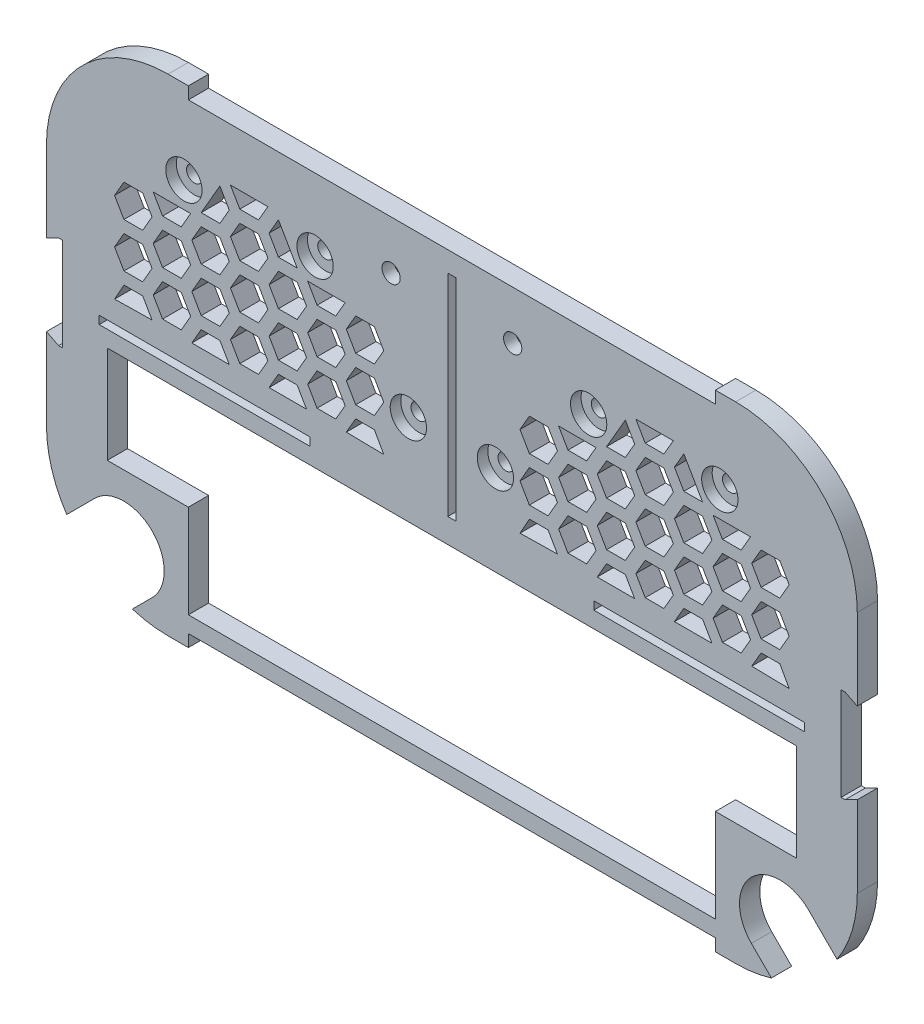
SolidWorks part; units mm, degrees
ref_plane "前视基准面" through (0, 0, 0) normal (0, 0, 1) x (1, 0, 0)
ref_plane "上视基准面" through (0, 0, 0) normal (0, 1, 0) x (1, 0, 0)
ref_plane "右视基准面" through (0, 0, 0) normal (1, 0, 0) x (0, 0, -1)
sketch "草图1" plane through (0, 0, 0) normal (0, 0, 1) x (1, 0, 0)
  line L1 (70, 60) -> (-70, 60)
  line L2 (-100, 30) -> (-100, -30)
  line L4 (70, -60) -> (-70, -60)
  line L5 (100, 30) -> (100, -30)
  arc A0 (-70, 60) -> (-100, 30) centre (-70, 30) ccw
  arc A1 (-70, -60) -> (-100, -30) centre (-70, -30) cw
  arc A2 (70, -60) -> (100, -30) centre (70, -30) ccw
  arc A3 (70, 60) -> (100, 30) centre (70, 30) cw
  point P12 (0, -60)
extrude "凸台-拉伸1" add sketch "草图1" along normal blind 5
sketch "草图2" plane through (0, 0, 0) normal (0, 0, 1) x (1, 0, 0)
  line L0 (95.0012, -46.5813) -> (95.0012, -58.6765)
  line L1 (88.021, -39.6011) -> (95.0012, -46.5813)
  line L2 (95.0012, -58.6765) -> (78.8123, -58.6765)
  line L3 (73.8789, -53.7432) -> (78.8123, -58.6765)
  line L5 (-73.8789, -53.7432) -> (-78.8123, -58.6765)
  line L6 (-95.0012, -58.6765) -> (-78.8123, -58.6765)
  line L7 (-88.021, -39.6011) -> (-95.0012, -46.5813)
  line L8 (-95.0012, -46.5813) -> (-95.0012, -58.6765)
  circle A0 centre (-80.95, 46.6721) radius 10
  circle A1 centre (80.95, 46.6721) radius 10
  arc A4 (70, -60) -> (100, -30) centre (70, -30) ccw construction
  arc A5 (-88.021, -39.6011) -> (-73.8789, -53.7432) centre (-80.95, -46.6721) cw
  arc A6 (88.021, -39.6011) -> (73.8789, -53.7432) centre (80.95, -46.6721) ccw
extrude "孔" cut sketch "草图2" along normal blind 4 contours A1 | A0 region at (-80.95, 46.6721, 0) region at (80.95, 46.6721, 0)
sketch "草图3" plane through (0, 0, 0) normal (0, 0, 1) x (1, 0, 0)
  line L8 (-85, -6) -> (-85, -30)
  line L12 (-70, -30) -> (-65, -30)
  line L22 (-85, -30) -> (-70, -30)
  line L26 (85, -30) -> (70, -30)
  line L32 (70, -30) -> (65, -30)
  line L37 (-65, -30) -> (-65, -53)
  line L39 (65, -53) -> (65, -30)
  line L40 (-65, -60) -> (-65, -57)
  line L41 (-70, -60) -> (70, -60) construction
  line L42 (-65, -57) -> (65, -57)
  line L43 (65, -57) -> (65, -60)
  line L44 (-65, -60) -> (65, -60)
  line L50 (-100, -10) -> (-97, -11.5)
  line L53 (-100, 10) -> (-100, -10)
  line L55 (-85, -6) -> (85, -6)
  line L56 (85, -6) -> (85, -30)
  line L88 (65, -53) -> (-65, -53)
  line L89 (87, 0) -> (87, -2)
  line L90 (87, -2) -> (35, -2)
  line L92 (87, 0) -> (37, 0)
  line L96 (35, 0) -> (35, -2)
  line L105 (-35, 0) -> (-35, -2)
  line L109 (-87, 0) -> (-37, 0)
  line L110 (-87, -2) -> (-35, -2)
  line L111 (-87, 0) -> (-87, -2)
  line L112 (97, 11.5) -> (96, 11.5)
  line L114 (-97, 11.5) -> (-100, 10)
  line L115 (97, 11.5) -> (100, 10)
  line L118 (100, 10) -> (100, -10)
  line L119 (100, -10) -> (97, -11.5)
  line L120 (96, 11.5) -> (96, -11.5)
  line L121 (96, -11.5) -> (97, -11.5)
  line L122 (-97, 11.5) -> (-96, 11.5)
  line L123 (-96, 11.5) -> (-96, -11.5)
  line L124 (-96, -11.5) -> (-97, -11.5)
  line L125 (0, 0) -> (-1, 0)
  line L126 (-1, 0) -> (-1, 50)
  line L128 (1, 50) -> (1, 0)
  line L129 (1, 0) -> (0, 0)
  line L130 (-1, 50) -> (-1, 52)
  line L131 (-1, 52) -> (1, 52)
  line L132 (1, 52) -> (1, 50)
  line L133 (-37, 0) -> (-35, 0)
  line L134 (35, 0) -> (37, 0)
  line L135 (-65, 57) -> (-65, 60)
  line L136 (-65, 57) -> (65, 57)
  line L138 (65, 57) -> (65, 60)
  line L139 (65, 60) -> (-65, 60)
extrude "切除-拉伸4" cut sketch "草图3" along normal up to next
hole_wizard "M3.5 六角头机械螺钉的柱形沉头孔1" positions "3D草图1" profile "草图4" counterbore size "M3.5" standard "ANSI Metric" end condition through all
sketch3d "3D草图1"
  point P31 (-66.0951, 39.3344, 5)
  point P33 (-33.736, 39.2649, 5)
  point P35 (-10.7334, 16.264, 5)
  point P78 (33.736, 39.2649, 5)
  point P80 (10.7334, 16.264, 5)
  point P82 (66.0951, 39.3344, 5)
sketch "草图4" plane through (-66.0951, 39.3344, 5) normal (1, 0, 0) x (0, -1, 0)
  line L0 (0, 0) -> (0, 5)
  line L1 (0, 5) -> (1.95, 5)
  line L3 (1.95, 5) -> (1.95, 2.6)
  line L4 (1.95, 2.6) -> (4.48, 2.6)
  line L5 (4.48, 2.6) -> (4.48, 0)
  line L7 (4.48, 0) -> (0, 0)
  line L11 (0, -6.35) -> (0, 107.95) construction
  dimension "通孔孔直径" = 3.9
  dimension "通孔孔深度" = 5
  dimension "柱形沉头孔直径" = 8.96
  dimension "柱形沉头孔深度" = 2.6
sketch "草图5" plane through (0, 0, 0) normal (0, 0, 1) x (1, 0, 0)
  line L4 (-35.8549, 5.5) -> (-38.1643, 9.5)
  line L6 (-38.1643, 9.5) -> (-42.7831, 9.5)
  line L13 (-42.7831, 9.5) -> (-45.0925, 5.5)
  line L17 (-26.3286, 11) -> (-28.638, 15)
  line L18 (-28.638, 15) -> (-33.2568, 15)
  line L19 (-33.2568, 15) -> (-35.5662, 11)
  line L20 (-35.5662, 11) -> (-33.2568, 7)
  line L21 (-33.2568, 7) -> (-28.638, 7)
  line L22 (-28.638, 7) -> (-26.3286, 11)
  line L23 (-16.8024, 16.5) -> (-19.1118, 20.5)
  line L24 (-19.1118, 20.5) -> (-23.7306, 20.5)
  line L25 (-23.7306, 20.5) -> (-26.04, 16.5)
  line L26 (-26.04, 16.5) -> (-23.7306, 12.5)
  line L27 (-23.7306, 12.5) -> (-19.1118, 12.5)
  line L28 (-19.1118, 12.5) -> (-16.8024, 16.5)
  line L29 (-35.8549, 16.5) -> (-38.1643, 20.5)
  line L30 (-38.1643, 20.5) -> (-42.7831, 20.5)
  line L31 (-42.7831, 20.5) -> (-45.0925, 16.5)
  line L32 (-45.0925, 16.5) -> (-42.7831, 12.5)
  line L33 (-42.7831, 12.5) -> (-38.1643, 12.5)
  line L34 (-38.1643, 12.5) -> (-35.8549, 16.5)
  line L35 (-26.3286, 22) -> (-28.638, 26)
  line L36 (-28.638, 26) -> (-33.2568, 26)
  line L37 (-33.2568, 26) -> (-35.5662, 22)
  line L38 (-35.5662, 22) -> (-33.2568, 18)
  line L39 (-33.2568, 18) -> (-28.638, 18)
  line L40 (-28.638, 18) -> (-26.3286, 22)
  line L41 (-16.8024, 27.5) -> (-19.1118, 31.5)
  line L42 (-19.1118, 31.5) -> (-23.7306, 31.5)
  line L43 (-23.7306, 31.5) -> (-26.04, 27.5)
  line L44 (-26.04, 27.5) -> (-23.7306, 23.5)
  line L45 (-23.7306, 23.5) -> (-19.1118, 23.5)
  line L46 (-19.1118, 23.5) -> (-16.8024, 27.5)
  line L47 (-35.8549, 27.5) -> (-38.1643, 31.5)
  line L48 (-38.1643, 31.5) -> (-42.7831, 31.5)
  line L49 (-42.7831, 31.5) -> (-45.0925, 27.5)
  line L50 (-45.0925, 27.5) -> (-42.7831, 23.5)
  line L51 (-42.7831, 23.5) -> (-38.1643, 23.5)
  line L52 (-38.1643, 23.5) -> (-35.8549, 27.5)
  line L56 (-35.5662, 33) -> (-33.2568, 29)
  line L57 (-33.2568, 29) -> (-28.638, 29)
  line L58 (-28.638, 29) -> (-26.3286, 33)
  line L67 (-42.7831, 42.5) -> (-45.0925, 38.5)
  line L68 (-45.0925, 38.5) -> (-42.7831, 34.5)
  line L69 (-42.7831, 34.5) -> (-38.1643, 34.5)
  line L83 (-45.3812, 11) -> (-47.6906, 15)
  line L84 (-47.6906, 15) -> (-52.3094, 15)
  line L85 (-52.3094, 15) -> (-54.6188, 11)
  line L86 (-54.6188, 11) -> (-52.3094, 7)
  line L87 (-52.3094, 7) -> (-47.6906, 7)
  line L88 (-47.6906, 7) -> (-45.3812, 11)
  line L89 (-45.3812, 22) -> (-47.6906, 26)
  line L90 (-47.6906, 26) -> (-52.3094, 26)
  line L91 (-52.3094, 26) -> (-54.6188, 22)
  line L92 (-54.6188, 22) -> (-52.3094, 18)
  line L93 (-52.3094, 18) -> (-47.6906, 18)
  line L94 (-47.6906, 18) -> (-45.3812, 22)
  line L95 (-45.3812, 33) -> (-47.6906, 37)
  line L96 (-47.6906, 37) -> (-52.3094, 37)
  line L97 (-52.3094, 37) -> (-54.6188, 33)
  line L98 (-54.6188, 33) -> (-52.3094, 29)
  line L99 (-52.3094, 29) -> (-47.6906, 29)
  line L100 (-47.6906, 29) -> (-45.3812, 33)
  line L125 (-42.7831, 42.5) -> (-38.1643, 34.5)
  line L126 (-35.5662, 33) -> (-26.3286, 33)
  line L127 (-45.0925, 5.5) -> (-35.8549, 5.5)
  line L129 (-54.9075, 5.5) -> (-64.1451, 5.5)
  line L130 (-64.4338, 33) -> (-73.6714, 33)
  line L131 (-57.2169, 42.5) -> (-61.8357, 34.5)
  line L132 (-57.2169, 34.5) -> (-61.8357, 34.5)
  line L133 (-54.9075, 38.5) -> (-57.2169, 34.5)
  line L134 (-57.2169, 42.5) -> (-54.9075, 38.5)
  line L135 (-71.362, 29) -> (-73.6714, 33)
  line L136 (-66.7432, 29) -> (-71.362, 29)
  line L137 (-64.4338, 33) -> (-66.7432, 29)
  line L138 (-61.8357, 23.5) -> (-64.1451, 27.5)
  line L139 (-57.2169, 23.5) -> (-61.8357, 23.5)
  line L140 (-54.9075, 27.5) -> (-57.2169, 23.5)
  line L141 (-57.2169, 31.5) -> (-54.9075, 27.5)
  line L142 (-61.8357, 31.5) -> (-57.2169, 31.5)
  line L143 (-64.1451, 27.5) -> (-61.8357, 31.5)
  line L144 (-80.8882, 23.5) -> (-83.1976, 27.5)
  line L145 (-76.2694, 23.5) -> (-80.8882, 23.5)
  line L146 (-73.96, 27.5) -> (-76.2694, 23.5)
  line L147 (-76.2694, 31.5) -> (-73.96, 27.5)
  line L148 (-80.8882, 31.5) -> (-76.2694, 31.5)
  line L149 (-83.1976, 27.5) -> (-80.8882, 31.5)
  line L150 (-71.362, 18) -> (-73.6714, 22)
  line L151 (-66.7432, 18) -> (-71.362, 18)
  line L152 (-64.4338, 22) -> (-66.7432, 18)
  line L153 (-66.7432, 26) -> (-64.4338, 22)
  line L154 (-71.362, 26) -> (-66.7432, 26)
  line L155 (-73.6714, 22) -> (-71.362, 26)
  line L156 (-61.8357, 12.5) -> (-64.1451, 16.5)
  line L157 (-57.2169, 12.5) -> (-61.8357, 12.5)
  line L158 (-54.9075, 16.5) -> (-57.2169, 12.5)
  line L159 (-57.2169, 20.5) -> (-54.9075, 16.5)
  line L160 (-61.8357, 20.5) -> (-57.2169, 20.5)
  line L161 (-64.1451, 16.5) -> (-61.8357, 20.5)
  line L162 (-80.8882, 12.5) -> (-83.1976, 16.5)
  line L163 (-76.2694, 12.5) -> (-80.8882, 12.5)
  line L164 (-73.96, 16.5) -> (-76.2694, 12.5)
  line L165 (-76.2694, 20.5) -> (-73.96, 16.5)
  line L166 (-80.8882, 20.5) -> (-76.2694, 20.5)
  line L167 (-83.1976, 16.5) -> (-80.8882, 20.5)
  line L168 (-71.362, 7) -> (-73.6714, 11)
  line L169 (-66.7432, 7) -> (-71.362, 7)
  line L170 (-64.4338, 11) -> (-66.7432, 7)
  line L171 (-66.7432, 15) -> (-64.4338, 11)
  line L172 (-71.362, 15) -> (-66.7432, 15)
  line L173 (-73.6714, 11) -> (-71.362, 15)
  line L174 (-57.2169, 9.5) -> (-54.9075, 5.5)
  line L175 (-61.8357, 9.5) -> (-57.2169, 9.5)
  line L176 (-64.1451, 5.5) -> (-61.8357, 9.5)
  line L181 (-52.3094, 40) -> (-47.6906, 40)
  line L184 (-52.3094, 44) -> (-54.6188, 44)
  line L185 (-54.6188, 44) -> (-52.3094, 40)
  line L186 (-52.3094, 44) -> (-45.3812, 44)
  line L187 (-45.3812, 44) -> (-47.6906, 40)
  line L188 (-21.4212, 9.5) -> (-23.7306, 9.5)
  line L191 (-26.04, 5.5) -> (-23.7306, 9.5)
  line L192 (-26.04, 5.5) -> (-16.8024, 5.3417)
  line L193 (-16.8024, 5.3417) -> (-19.1118, 9.5)
  line L194 (-19.1118, 9.5) -> (-21.4212, 9.5)
  line L195 (-80.8882, 9.5) -> (-78.5788, 9.5)
  line L196 (-83.1976, 5.3417) -> (-80.8882, 9.5)
  line L197 (-73.96, 5.5) -> (-83.1976, 5.3417)
  line L198 (-73.96, 5.5) -> (-76.2694, 9.5)
  line L199 (-78.5788, 9.5) -> (-76.2694, 9.5)
  line L200 (78.5788, 9.5) -> (76.2694, 9.5)
  line L201 (73.96, 5.5) -> (76.2694, 9.5)
  line L202 (73.96, 5.5) -> (83.1976, 5.3417)
  line L203 (83.1976, 5.3417) -> (80.8882, 9.5)
  line L204 (80.8882, 9.5) -> (78.5788, 9.5)
  line L205 (19.1118, 9.5) -> (21.4212, 9.5)
  line L206 (16.8024, 5.3417) -> (19.1118, 9.5)
  line L207 (26.04, 5.5) -> (16.8024, 5.3417)
  line L208 (26.04, 5.5) -> (23.7306, 9.5)
  line L209 (21.4212, 9.5) -> (23.7306, 9.5)
  line L210 (45.3812, 44) -> (47.6906, 40)
  line L211 (52.3094, 44) -> (45.3812, 44)
  line L212 (54.6188, 44) -> (52.3094, 40)
  line L213 (52.3094, 44) -> (54.6188, 44)
  line L214 (52.3094, 40) -> (47.6906, 40)
  line L215 (64.1451, 5.5) -> (61.8357, 9.5)
  line L216 (61.8357, 9.5) -> (57.2169, 9.5)
  line L217 (57.2169, 9.5) -> (54.9075, 5.5)
  line L218 (73.6714, 11) -> (71.362, 15)
  line L219 (71.362, 15) -> (66.7432, 15)
  line L220 (66.7432, 15) -> (64.4338, 11)
  line L221 (64.4338, 11) -> (66.7432, 7)
  line L222 (66.7432, 7) -> (71.362, 7)
  line L223 (71.362, 7) -> (73.6714, 11)
  line L224 (83.1976, 16.5) -> (80.8882, 20.5)
  line L225 (80.8882, 20.5) -> (76.2694, 20.5)
  line L226 (76.2694, 20.5) -> (73.96, 16.5)
  line L227 (73.96, 16.5) -> (76.2694, 12.5)
  line L228 (76.2694, 12.5) -> (80.8882, 12.5)
  line L229 (80.8882, 12.5) -> (83.1976, 16.5)
  line L230 (64.1451, 16.5) -> (61.8357, 20.5)
  line L231 (61.8357, 20.5) -> (57.2169, 20.5)
  line L232 (57.2169, 20.5) -> (54.9075, 16.5)
  line L233 (54.9075, 16.5) -> (57.2169, 12.5)
  line L234 (57.2169, 12.5) -> (61.8357, 12.5)
  line L235 (61.8357, 12.5) -> (64.1451, 16.5)
  line L236 (73.6714, 22) -> (71.362, 26)
  line L237 (71.362, 26) -> (66.7432, 26)
  line L238 (66.7432, 26) -> (64.4338, 22)
  line L239 (64.4338, 22) -> (66.7432, 18)
  line L240 (66.7432, 18) -> (71.362, 18)
  line L241 (71.362, 18) -> (73.6714, 22)
  line L242 (83.1976, 27.5) -> (80.8882, 31.5)
  line L243 (80.8882, 31.5) -> (76.2694, 31.5)
  line L244 (76.2694, 31.5) -> (73.96, 27.5)
  line L245 (73.96, 27.5) -> (76.2694, 23.5)
  line L246 (76.2694, 23.5) -> (80.8882, 23.5)
  line L247 (80.8882, 23.5) -> (83.1976, 27.5)
  line L248 (64.1451, 27.5) -> (61.8357, 31.5)
  line L249 (61.8357, 31.5) -> (57.2169, 31.5)
  line L250 (57.2169, 31.5) -> (54.9075, 27.5)
  line L251 (54.9075, 27.5) -> (57.2169, 23.5)
  line L252 (57.2169, 23.5) -> (61.8357, 23.5)
  line L253 (61.8357, 23.5) -> (64.1451, 27.5)
  line L254 (64.4338, 33) -> (66.7432, 29)
  line L255 (66.7432, 29) -> (71.362, 29)
  line L256 (71.362, 29) -> (73.6714, 33)
  line L257 (57.2169, 42.5) -> (54.9075, 38.5)
  line L258 (54.9075, 38.5) -> (57.2169, 34.5)
  line L259 (57.2169, 34.5) -> (61.8357, 34.5)
  line L260 (57.2169, 42.5) -> (61.8357, 34.5)
  line L261 (64.4338, 33) -> (73.6714, 33)
  line L262 (54.9075, 5.5) -> (64.1451, 5.5)
  line L263 (45.0925, 5.5) -> (35.8549, 5.5)
  line L264 (35.5662, 33) -> (26.3286, 33)
  line L265 (42.7831, 42.5) -> (38.1643, 34.5)
  line L266 (47.6906, 29) -> (45.3812, 33)
  line L267 (52.3094, 29) -> (47.6906, 29)
  line L268 (54.6188, 33) -> (52.3094, 29)
  line L269 (52.3094, 37) -> (54.6188, 33)
  line L270 (47.6906, 37) -> (52.3094, 37)
  line L271 (45.3812, 33) -> (47.6906, 37)
  line L272 (47.6906, 18) -> (45.3812, 22)
  line L273 (52.3094, 18) -> (47.6906, 18)
  line L274 (54.6188, 22) -> (52.3094, 18)
  line L275 (52.3094, 26) -> (54.6188, 22)
  line L276 (47.6906, 26) -> (52.3094, 26)
  line L277 (45.3812, 22) -> (47.6906, 26)
  line L278 (47.6906, 7) -> (45.3812, 11)
  line L279 (52.3094, 7) -> (47.6906, 7)
  line L280 (54.6188, 11) -> (52.3094, 7)
  line L281 (52.3094, 15) -> (54.6188, 11)
  line L282 (47.6906, 15) -> (52.3094, 15)
  line L283 (45.3812, 11) -> (47.6906, 15)
  line L284 (42.7831, 34.5) -> (38.1643, 34.5)
  line L285 (45.0925, 38.5) -> (42.7831, 34.5)
  line L286 (42.7831, 42.5) -> (45.0925, 38.5)
  line L287 (28.638, 29) -> (26.3286, 33)
  line L288 (33.2568, 29) -> (28.638, 29)
  line L289 (35.5662, 33) -> (33.2568, 29)
  line L290 (38.1643, 23.5) -> (35.8549, 27.5)
  line L291 (42.7831, 23.5) -> (38.1643, 23.5)
  line L292 (45.0925, 27.5) -> (42.7831, 23.5)
  line L293 (42.7831, 31.5) -> (45.0925, 27.5)
  line L294 (38.1643, 31.5) -> (42.7831, 31.5)
  line L295 (35.8549, 27.5) -> (38.1643, 31.5)
  line L296 (19.1118, 23.5) -> (16.8024, 27.5)
  line L297 (23.7306, 23.5) -> (19.1118, 23.5)
  line L298 (26.04, 27.5) -> (23.7306, 23.5)
  line L299 (23.7306, 31.5) -> (26.04, 27.5)
  line L300 (19.1118, 31.5) -> (23.7306, 31.5)
  line L301 (16.8024, 27.5) -> (19.1118, 31.5)
  line L302 (28.638, 18) -> (26.3286, 22)
  line L303 (33.2568, 18) -> (28.638, 18)
  line L304 (35.5662, 22) -> (33.2568, 18)
  line L305 (33.2568, 26) -> (35.5662, 22)
  line L306 (28.638, 26) -> (33.2568, 26)
  line L307 (26.3286, 22) -> (28.638, 26)
  line L308 (38.1643, 12.5) -> (35.8549, 16.5)
  line L309 (42.7831, 12.5) -> (38.1643, 12.5)
  line L310 (45.0925, 16.5) -> (42.7831, 12.5)
  line L311 (42.7831, 20.5) -> (45.0925, 16.5)
  line L312 (38.1643, 20.5) -> (42.7831, 20.5)
  line L313 (35.8549, 16.5) -> (38.1643, 20.5)
  line L314 (19.1118, 12.5) -> (16.8024, 16.5)
  line L315 (23.7306, 12.5) -> (19.1118, 12.5)
  line L316 (26.04, 16.5) -> (23.7306, 12.5)
  line L317 (23.7306, 20.5) -> (26.04, 16.5)
  line L318 (19.1118, 20.5) -> (23.7306, 20.5)
  line L319 (16.8024, 16.5) -> (19.1118, 20.5)
  line L320 (28.638, 7) -> (26.3286, 11)
  line L321 (33.2568, 7) -> (28.638, 7)
  line L322 (35.5662, 11) -> (33.2568, 7)
  line L323 (33.2568, 15) -> (35.5662, 11)
  line L324 (28.638, 15) -> (33.2568, 15)
  line L325 (26.3286, 11) -> (28.638, 15)
  line L326 (42.7831, 9.5) -> (45.0925, 5.5)
  line L327 (38.1643, 9.5) -> (42.7831, 9.5)
  line L328 (35.8549, 5.5) -> (38.1643, 9.5)
extrude "切除-拉伸5" cut sketch "草图5" against normal through all and the other way through all
ref_plane "基准面1" through (0, 0, 0) normal (0, 0, -1) x (-1, 0, 0)
sketch "草图8" plane through (0, 0, 0) normal (0, 0, 1) x (1, 0, 0)
  line L5 (-26, 52) -> (-26, 47)
  line L8 (-26, 47) -> (-66, 47)
  line L9 (-66, 47) -> (-66, 52)
  line L10 (-66, 52) -> (-26, 52)
  line L46 (66, 52) -> (26, 52)
  line L47 (66, 47) -> (66, 52)
  line L48 (26, 47) -> (66, 47)
  line L50 (26, 52) -> (26, 47)
extrude "切除-拉伸7" cut sketch "草图8" along normal blind 3
hole_wizard "M4 六角凹头盖的柱孔1" positions "3D草图4" profile "草图11" counterbore size "M4" standard "BSI" end condition through all
sketch3d "3D草图4"
  line L5 (15, 45, 3) -> (-15, 45, 3)
  line L6 (15, 45, 3) -> (15, 45, 0) construction
  line L7 (-15, 45, 3) -> (-15, 45, 0) construction
  point P17 (15, 45, 0)
  point P19 (-15, 45, 0)
sketch "草图11" plane through (-15, 45, 0) normal (1, 0, 0) x (0, 1, 0)
  line L0 (0, 0) -> (0, 5)
  line L1 (0, 5) -> (2.25, 5)
  line L3 (2.25, 5) -> (2.25, 2)
  line L4 (2.25, 2) -> (4, 2)
  line L5 (4, 2) -> (4, 0)
  line L7 (4, 0) -> (0, 0)
  line L11 (0, -6.35) -> (0, 107.95) construction
  dimension "通孔孔直径" = 4.5
  dimension "通孔孔深度" = 5
  dimension "柱形沉头孔直径" = 8
  dimension "柱形沉头孔深度" = 2
extrude "切除-拉伸8" cut sketch "草图2<8>" along normal blind 10 contours L1 A6 L3 L2 L0 | A5 L7 L8 L6 L5 region at (83.1956, -48.4377, 0) region at (-83.1956, -48.4377, 0)
sketch "草图2<8>" plane through (0, 0, 0) normal (0, 0, 1) x (1, 0, 0) same geometry as "草图2"
